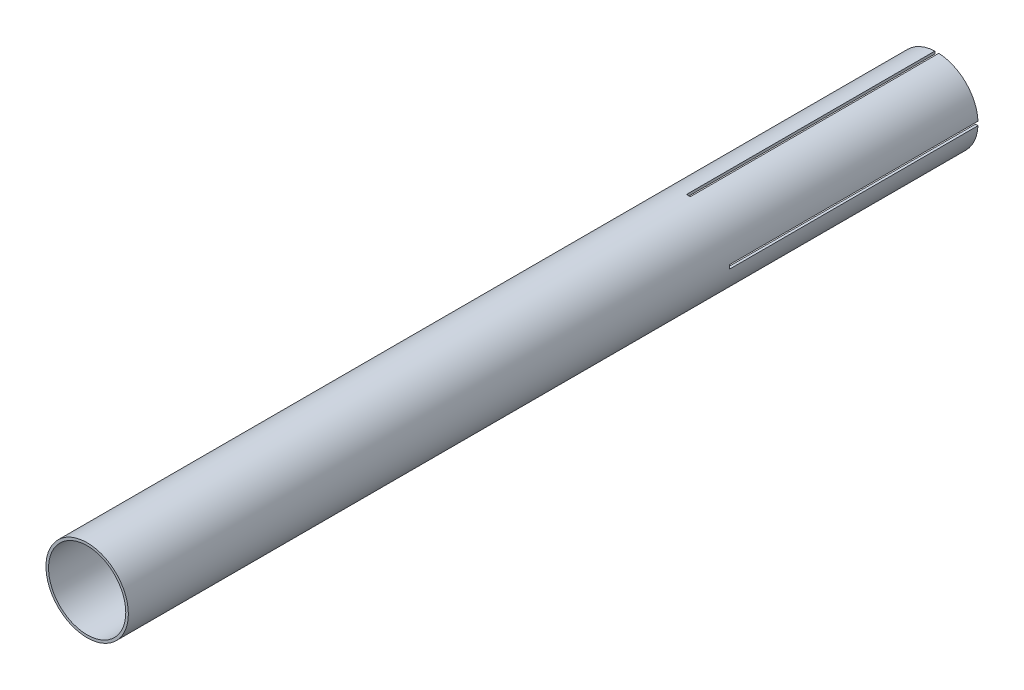
SolidWorks part; units mm, degrees
ref_plane "Front Plane" through (0, 0, 0) normal (0, 0, 1) x (1, 0, 0)
ref_plane "Top Plane" through (0, 0, 0) normal (0, 1, 0) x (1, 0, 0)
ref_plane "Right Plane" through (0, 0, 0) normal (1, 0, 0) x (0, 0, -1)
sketch "Sketch1" plane through (0, 0, 0) normal (0, 0, 1) x (1, 0, 0)
  circle A1 centre (0, 0) radius 30
  circle A2 centre (0, 0) radius 32
extrude "Boss-Extrude1" add sketch "Sketch1" along normal blind 660
sketch "Sketch2" plane through (0, 0, 0) normal (0, 1, 0) x (1, 0, 0)
  line L0 (32, 0) -> (-32, 0) construction
  line L1 (-1.5, 0) -> (1.5, 0)
  line L2 (-1.5, 0) -> (-1.5, -193)
  line L3 (-1.5, -193) -> (1.5, -193)
  line L4 (1.5, 0) -> (1.5, -193)
  dimension "D1" = 3
  dimension "D2" = 1.5
  dimension "D3" = 0
  dimension "D4" = 193
extrude "Cut-Extrude1" cut sketch "Sketch2" against normal up to next
ref_axis "Axis1" through (0, 0, 660) along (0, 0, -1)
pattern_circular "CirPattern1" count 4 every 90 about axis through (0, 0, 660) along (0, 0, -1) of "Cut-Extrude1"
